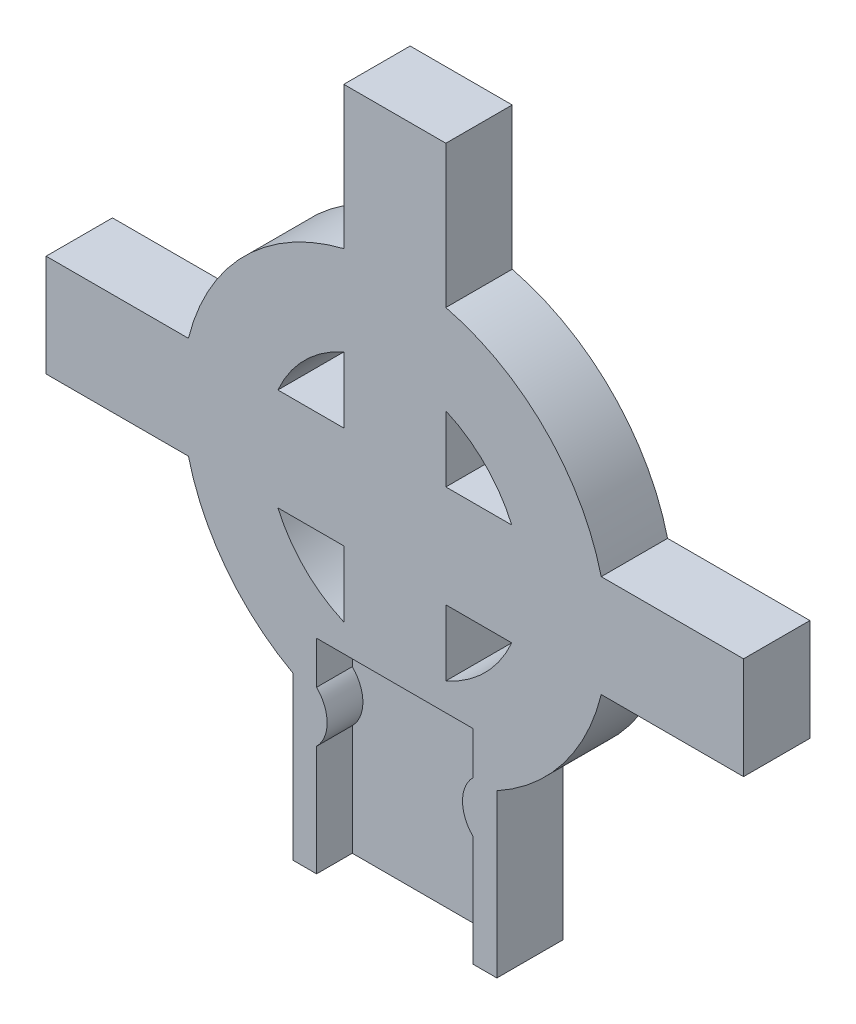
SolidWorks part; units mm, degrees
ref_plane "Alzado" through (0, 0, 0) normal (0, 0, 1) x (1, 0, 0)
ref_plane "Planta" through (0, 0, 0) normal (0, 1, 0) x (1, 0, 0)
ref_plane "Vista lateral" through (0, 0, 0) normal (1, 0, 0) x (0, 0, -1)
sketch "Croquis1" plane through (0, 0, 0) normal (0, 0, 1) x (1, 0, 0)
  line L0 (-6, 13) -> (-6, 20.5) construction
  line L1 (0, 0) -> (-12, 0)
  line L2 (0, 0) -> (0, 9.5341)
  line L4 (-12, 0) -> (-12, 9.5341)
  line L5 (14.5, 17.5) -> (6.1347, 17.5)
  line L6 (-26.5, 17.5) -> (-26.5, 23.5)
  line L7 (-26.5, 20.5) -> (-6, 20.5) construction
  line L8 (14.5, 23.5) -> (6.1347, 23.5)
  line L9 (14.5, 17.5) -> (14.5, 23.5)
  line L10 (-9, 23.5) -> (-9, 27.3739)
  line L11 (-9, 41) -> (-3, 41)
  line L12 (-3, 23.5) -> (-3, 27.3739)
  line L13 (-9, 17.5) -> (-9, 13.6261)
  line L14 (-3, 17.5) -> (-3, 13.6261)
  line L15 (-9, 17.5) -> (-12.8739, 17.5)
  line L16 (-9, 23.5) -> (-12.8739, 23.5)
  line L17 (-18.1347, 17.5) -> (-26.5, 17.5)
  line L18 (-18.1347, 23.5) -> (-26.5, 23.5)
  line L19 (-9, 32.6347) -> (-9, 41)
  line L20 (-3, 32.6347) -> (-3, 41)
  line L21 (0.8739, 17.5) -> (-3, 17.5)
  line L22 (0.8739, 23.5) -> (-3, 23.5)
  arc A0 (-9, 32.6347) -> (-18.1347, 23.5) centre (-6, 20.5) ccw
  arc A1 (-9, 27.3739) -> (-12.8739, 23.5) centre (-6, 20.5) ccw
  arc A2 (-18.1347, 17.5) -> (-12, 9.5341) centre (-6, 20.5) ccw
  arc A3 (-12.8739, 17.5) -> (-9, 13.6261) centre (-6, 20.5) ccw
  arc A4 (-3, 13.6261) -> (0.8739, 17.5) centre (-6, 20.5) ccw
  arc A5 (0.8739, 23.5) -> (-3, 27.3739) centre (-6, 20.5) ccw
  arc A6 (0, 9.5341) -> (6.1347, 17.5) centre (-6, 20.5) ccw
  arc A7 (6.1347, 23.5) -> (-3, 32.6347) centre (-6, 20.5) ccw
  point P15 (-6, 17.5)
  point P16 (-6, 23.5)
  point P22 (-6, 41)
  dimension "D3" = 25
  dimension "D4" = 5
  dimension "D5" = 3
  dimension "D6" = 20.5
  dimension "D7" = 3
extrude "Saliente-Extruir1" add sketch "Croquis1" along normal blind 3.9
sketch "Croquis2" plane through (0, 0, 3.9) normal (0, 0, 1) x (1, 0, 0)
  line L0 (-12, 0) -> (0, 0) construction
  line L1 (-10.6, 0) -> (-1.4, 0)
  line L2 (-10.6, 0) -> (-10.6, 6.5)
  line L3 (-10.6, 12) -> (-1.4, 12)
  line L4 (-1.4, 0) -> (-1.4, 6.5)
  line L5 (-6, 12) -> (-6, 0) construction
  line L6 (-10.6, 9.5) -> (-10.6, 12)
  line L7 (-1.4, 9.5) -> (-1.4, 12)
  arc A1 (-10.6, 9.5) -> (-10.6, 6.5) centre (-12.1, 8) cw
  arc A2 (-1.4, 9.5) -> (-1.4, 6.5) centre (0.1, 8) ccw
  point P6 (-6, 0)
  point P7 (-6, 0)
  dimension "D1" = 9.2
  dimension "D2" = 12
  dimension "D3" = 4
  dimension "D4" = 3
  dimension "D5" = 1.5
extrude "Cortar-Extruir1" cut sketch "Croquis2" against normal blind 2.1
